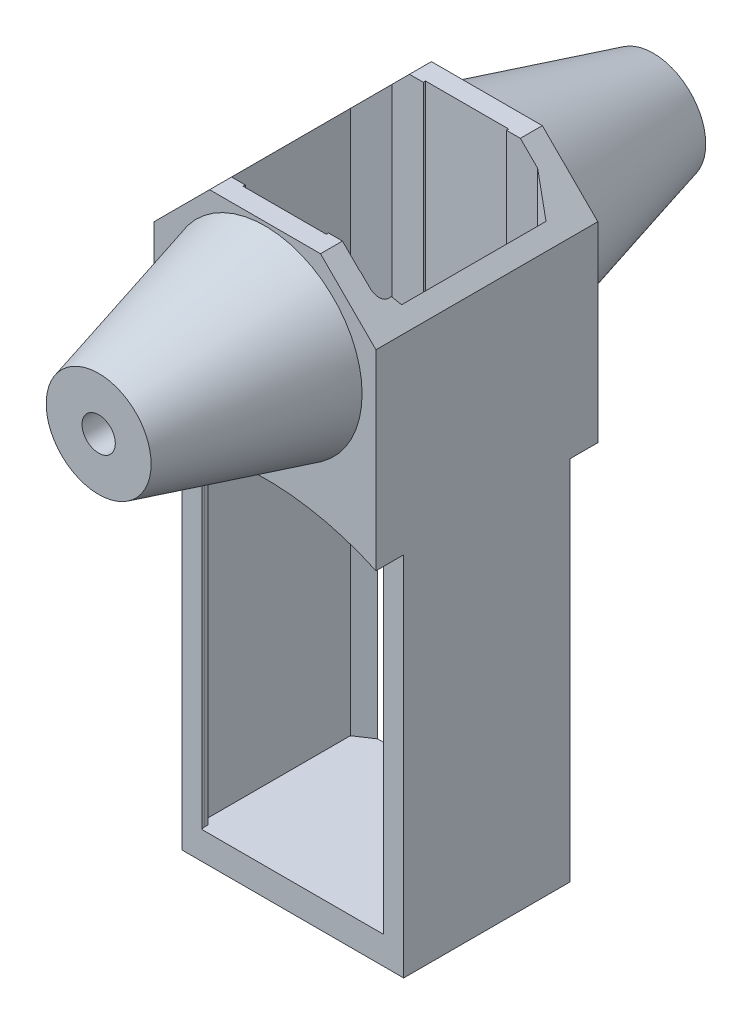
SolidWorks part; units mm, degrees
ref_plane "Front Plane" through (0, 0, 0) normal (0, 0, 1) x (1, 0, 0)
ref_plane "Top Plane" through (0, 0, 0) normal (0, 1, 0) x (1, 0, 0)
ref_plane "Right Plane" through (0, 0, 0) normal (1, 0, 0) x (0, 0, -1)
sketch "Sketch1" plane through (0, 0, 0) normal (0, 1, 0) x (1, 0, 0)
  line L0 (4.7625, -10.1854) -> (8.3298, -10.1854)
  line L5 (-4.7625, 10.1854) -> (-4.7625, 10.4394)
  line L6 (-12.7, -12.7) -> (12.7, -12.7)
  line L7 (4.7625, 10.1854) -> (8.3298, 10.1854)
  line L8 (-8.3298, 10.1854) -> (-11.2014, 8.271)
  line L9 (-8, 10.1) -> (-11, 8.1) construction
  line L10 (0, 0) -> (-11.2014, 0) construction
  line L11 (0, 0) -> (0, 10.4394) construction
  line L12 (-8.3298, -10.1854) -> (-8.3769, -10.154)
  line L13 (8.3298, -10.1854) -> (8.3769, -10.154)
  line L14 (8.3298, 10.1854) -> (11.2014, 8.271)
  line L15 (-8.3298, 10.1854) -> (-4.7625, 10.1854)
  line L16 (-12.7, 12.7) -> (-12.7, -12.7)
  line L17 (12.7, 12.7) -> (12.7, -12.7)
  line L34 (-10.504, -8.7359) -> (-11.2014, -8.271)
  line L35 (8.3769, -10.154) -> (9.4165, -10.154)
  line L36 (9.5863, -10.1409) -> (9.6154, -10.1409)
  line L37 (-9.5863, -10.1409) -> (-9.6154, -10.1409)
  line L38 (-8.75, -10.154) -> (-9.4165, -10.154)
  line L39 (-10.504, -9.1) -> (-10.504, -8.9)
  line L40 (-9.5863, -10.1409) -> (-9.6154, -10.1409)
  line L41 (-8.3769, -10.154) -> (-9.4165, -10.154)
  line L42 (-10.504, -9.1) -> (-10.504, -8.7359)
  line L43 (10.504, -9.1) -> (10.504, -8.7359)
  line L44 (10.504, -8.7359) -> (11.2014, -8.271)
  line L284 (-12.7, 12.7) -> (12.7, 12.7)
  line L286 (-12.7, -12.7) -> (12.7, 12.7) construction
  line L287 (-12.7, 12.7) -> (12.7, -12.7) construction
  line L288 (-8.3298, -10.1854) -> (-4.7625, -10.1854)
  line L289 (-11.2014, -8.271) -> (-11.2014, 8.271)
  line L291 (11.2014, -8.271) -> (11.2014, 8.271)
  line L326 (-4.7625, 10.4394) -> (4.7625, 10.4394)
  line L327 (4.7625, 10.4394) -> (4.7625, 10.1854)
  line L328 (-4.7625, -10.1854) -> (-4.7625, -10.4394)
  line L335 (-4.7625, -10.4394) -> (4.7625, -10.4394)
  line L338 (4.7625, -10.4394) -> (4.7625, -10.1854)
  arc A7 (9.5863, -10.1409) -> (9.4165, -10.154) centre (9.4168, -9.0458) cw
  arc A8 (-9.5863, -10.1409) -> (-9.4165, -10.154) centre (-9.4168, -9.0458) ccw
  arc A9 (-10.504, -9.1) -> (-9.6154, -10.1409) centre (-9.45, -9.1) ccw
  arc A10 (-9.5863, -10.1409) -> (-9.4165, -10.154) centre (-9.4168, -9.0458) ccw
  arc A11 (-10.504, -9.1) -> (-9.6154, -10.1409) centre (-9.45, -9.1) ccw
  arc A12 (10.504, -9.1) -> (9.6154, -10.1409) centre (9.45, -9.1) cw
  point P0 (0, 0)
  point P6 (0, 0)
  point P15 (0, 10.4394)
  point P23 (0, -10.4394)
  dimension "D1" = 25.4
  dimension "D2" = 25.4
  dimension "D3" = 0.254
  dimension "D5" = 9.525
  dimension "D6" = 22.4028
  dimension "D7" = 0.254
  dimension "D8" = 20.3708
  dimension "D9" = 0.254
  dimension "D15" = 0.254
extrude "Boss-Extrude1" add sketch "Sketch1" along normal blind 67.056
sketch "Sketch4" plane through (0, 0, 0) normal (0, -1, 0) x (-1, 0, 0)
  line L1 (12.7, -12.7) -> (-12.7, -12.7)
  line L2 (12.7, -12.7) -> (12.7, 12.7)
  line L3 (12.7, 12.7) -> (-12.7, 12.7)
  line L4 (-12.7, -12.7) -> (-12.7, 12.7)
extrude "Boss-Extrude4" add sketch "Sketch4" along normal blind 3.175
sketch "Sketch5" plane through (0, 0, -12.7) normal (0, 0, -1) x (-1, 0, 0)
  circle A0 centre (0, 11.43) radius 30.1625
  dimension "D2" = 60.325
  dimension "D1" = 11.43
extrude "Cut-Extrude1" cut sketch "Sketch5" against normal blind 3.175
mirror "Mirror1" about plane through (0, 0, 0) normal (0, 0, 1) of "Cut-Extrude1"
sketch "Sketch7" plane through (0, 0, 12.7) normal (0, 0, 1) x (1, 0, 0)
  circle A0 centre (0, 55.5371) radius 11.1125
  circle A1 centre (0, 11.0871) radius 4.7625 construction
  dimension "D2" = 22.225
  dimension "D1" = 44.45
extrude "Boss-Extrude6" add sketch "Sketch7" along normal blind 19.05 draft 15
sketch "Sketch8" plane through (0, 0, 31.75) normal (0, 0, 1) x (1, 0, 0)
  circle A0 centre (0, 55.5371) radius 1.905
  dimension "D1" = 3.81
extrude "Cut-Extrude2" cut sketch "Sketch8" against normal blind 12.7
mirror "Mirror3" about plane through (0, 0, 0) normal (0, 0, 1) of "Cut-Extrude2", "Boss-Extrude6"
chamfer "Chamfer3" distance 6.35 angle 45 2 edges at (-12.7, 67.056, 0) (12.7, 67.056, 0)
